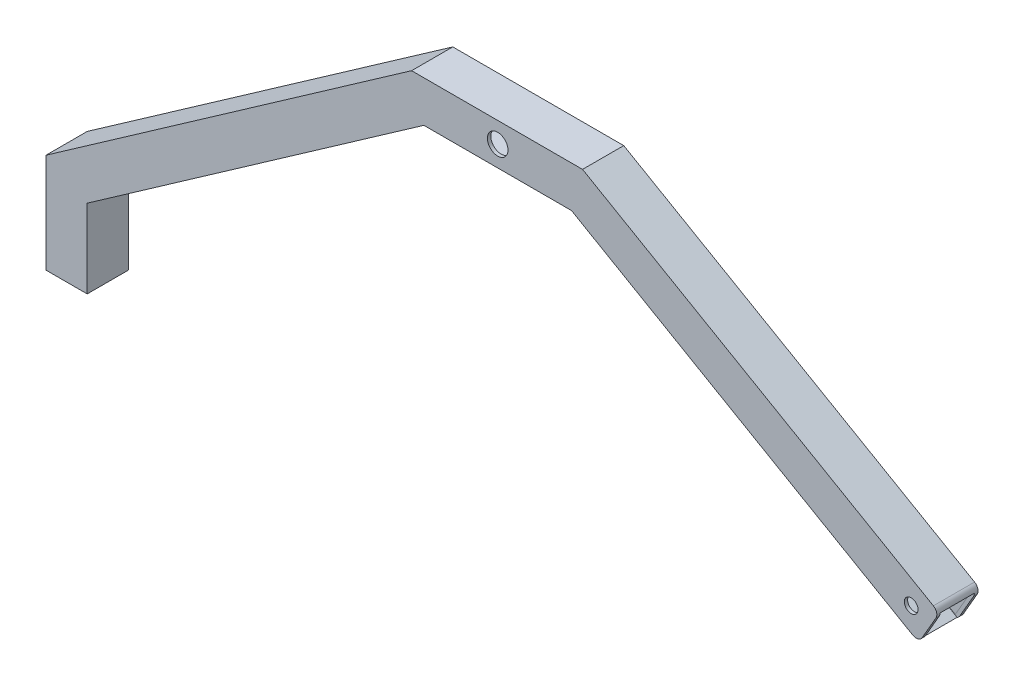
SolidWorks part; units mm, degrees
material "1060 Alloy"
ref_plane "Front Plane" through (0, 0, 0) normal (0, 0, 1) x (1, 0, 0)
ref_plane "Top Plane" through (0, 0, 0) normal (0, 1, 0) x (1, 0, 0)
ref_plane "Right Plane" through (0, 0, 0) normal (1, 0, 0) x (0, 0, -1)
sketch "Sketch2" plane through (0, 0, 0) normal (0, 0, 1) x (1, 0, 0)
  line L2 (-28.0029, 3.2102) -> (-134.4927, -71.3547)
  line L3 (-28.0029, 3.2102) -> (21.7951, 3.2102)
  line L5 (-24.4214, -8.7883) -> (18.5771, -8.7883)
  line L7 (-134.4927, -100.3547) -> (-122.4927, -100.3547) construction
  line L10 (-122.4927, -77.4585) -> (-24.4214, -8.7883)
  line L13 (-134.4927, -71.3547) -> (-134.4927, -100.3547)
  line L14 (-134.4927, -100.3547) -> (-122.4927, -100.3547)
  line L15 (-122.4927, -77.4585) -> (-122.4927, -100.3547)
  line L16 (21.7951, 3.2102) -> (125.7181, -56.7898)
  line L17 (125.7181, -56.7898) -> (119.7181, -67.1821)
  line L18 (119.7181, -67.1821) -> (18.5771, -8.7883)
  line L38 (-134.4927, -100.3547) -> (-122.4927, -100.3547)
  point P2 (0, 1.2778)
  point P6 (0, 1.2778)
  dimension "D2" = 29
  dimension "D3" = 12
  dimension "D4" = 130
  dimension "D5" = 145
  dimension "D7" = 120
  dimension "D8" = 150
  dimension "D9" = 90
  dimension "D10" = 12
extrude "Boss-Extrude1" add sketch "Sketch2" along normal blind 12 contours L18 L17 L16 L3 L2 L13 L14 L15 L10 L5 region at (-3.1039, 0.4096, 0)
shell "Shell1" thickness 1 removed face at (-128.4927, -100.3547, 6)
sketch "Sketch3" plane through (0, 0, 12) normal (0, 0, 1) x (1, 0, 0)
  line L0 (-24.4214, -8.7883) -> (18.5771, -8.7883) construction
  line L1 (119.7181, -67.1821) -> (18.5771, -8.7883) construction
  line L2 (125.7181, -56.7898) -> (119.7181, -67.1821) construction
  circle A0 centre (-2.9222, -2.7883) radius 3
  circle A1 centre (117.5219, -58.9859) radius 2
  dimension "D1" = 6
  dimension "D3" = 4
  dimension "D2" = 6
  dimension "D4" = 6
  dimension "D5" = 6
extrude "Cut-Extrude1" cut sketch "Sketch3" against normal blind 12
sketch "Sketch4" plane through (118.8793, -68.635, 0) normal (0.866, -0.5, 0) x (0, 0, -1)
  line L1 (-11.0371, 12.6336) -> (-1.0371, 12.6336)
  line L2 (-11.0371, 12.6336) -> (-11.0371, 2.6336)
  line L3 (-11.0371, 2.6336) -> (-1.0371, 2.6336)
  line L4 (-1.0371, 12.6336) -> (-1.0371, 2.6336)
  line L5 (-11.0371, 12.6336) -> (-1.0371, 2.6336) construction
  line L6 (-11.0371, 2.6336) -> (-1.0371, 12.6336) construction
  point P0 (-6.0371, 7.6336)
  dimension "D1" = 10
  dimension "D2" = 10
extrude "Cut-Extrude2" cut sketch "Sketch4" against normal blind 12
fillet "Fillet1" radius 2 2 edges at (119.7181, -67.1821, 6) (125.7181, -56.7898, 6)
